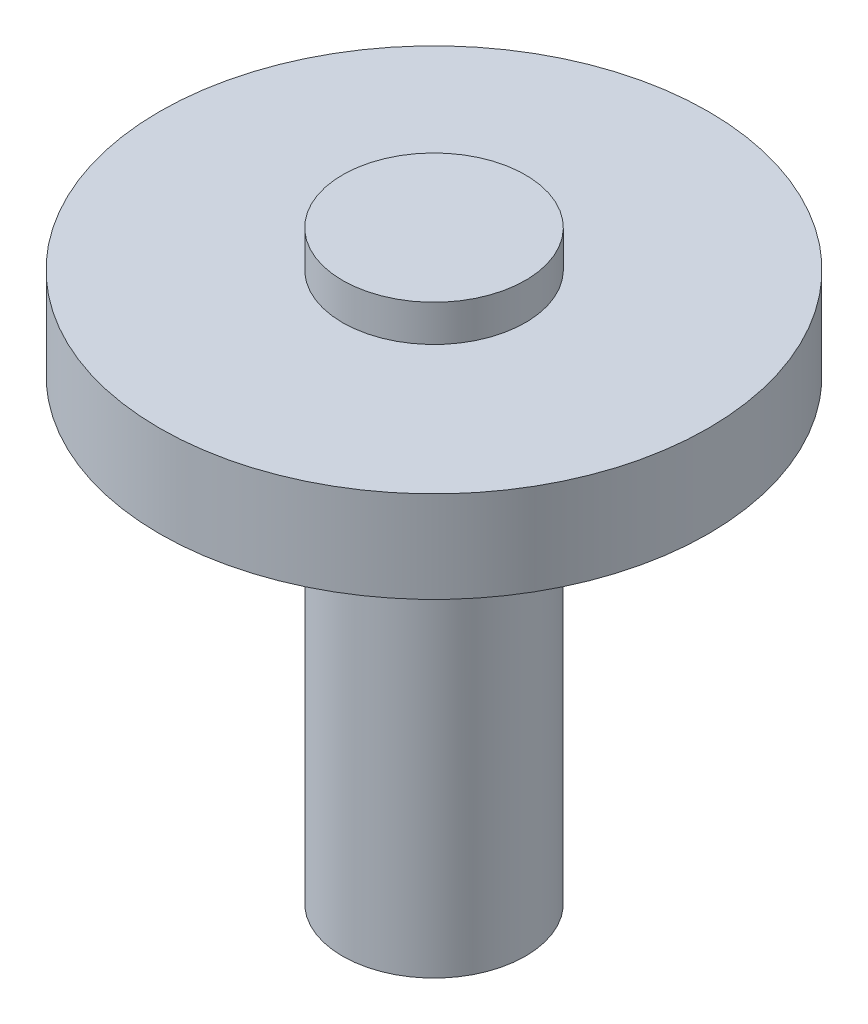
SolidWorks part; units mm, degrees
material "6061 Alloy"
ref_plane "Plano frontal" through (0, 0, 0) normal (0, 0, 1) x (1, 0, 0)
ref_plane "Plano superior" through (0, 0, 0) normal (0, 1, 0) x (1, 0, 0)
ref_plane "Plano direito" through (0, 0, 0) normal (1, 0, 0) x (0, 0, -1)
sketch "Sketch1" plane through (0, 0, 0) normal (0, 1, 0) x (1, 0, 0)
  circle A0 centre (0, 0) radius 15
  dimension "D1" = 30
extrude "Boss-Extrude1" add sketch "Sketch1" along normal blind 5
sketch "Sketch3" plane through (0, 5, 0) normal (0, 1, 0) x (1, 0, 0)
  circle A1 centre (0, 0) radius 5
  dimension "D1" = 10
extrude "Boss-Extrude2" add sketch "Sketch3" along normal blind 2
sketch "Sketch2" plane through (0, 0, 0) normal (0, -1, 0) x (1, 0, 0)
  circle A0 centre (0, 0) radius 5
  dimension "D1" = 10
extrude "Boss-Extrude3" add sketch "Sketch2" along normal blind 25
